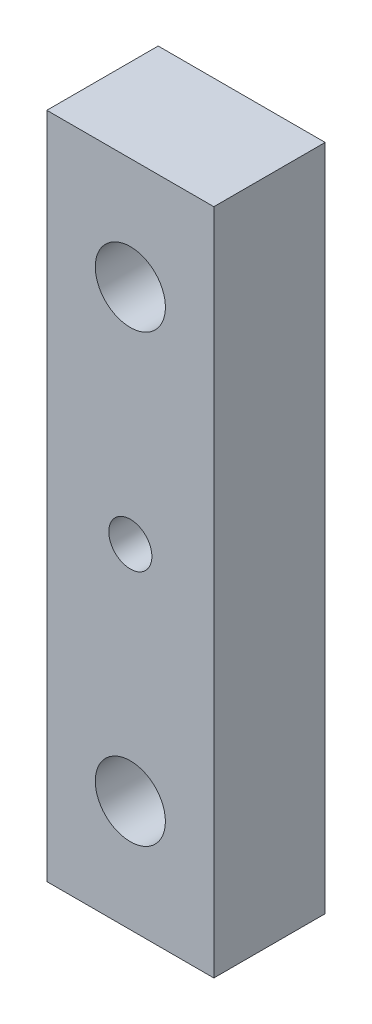
SolidWorks part; units mm, degrees
ref_plane "Front Plane" through (0, 0, 0) normal (0, 0, 1) x (1, 0, 0)
ref_plane "Top Plane" through (0, 0, 0) normal (0, 1, 0) x (1, 0, 0)
ref_plane "Right Plane" through (0, 0, 0) normal (1, 0, 0) x (0, 0, -1)
sketch "Sketch1" plane through (0, 0, 0) normal (0, 0, 1) x (1, 0, 0)
  line L1 (0, 0) -> (19.05, 0)
  line L2 (0, 0) -> (0, 76.2)
  line L3 (0, 76.2) -> (19.05, 76.2)
  line L4 (19.05, 0) -> (19.05, 76.2)
  dimension "D1" = 19.05
  dimension "D2" = 76.2
extrude "Extrude1" add sketch "Sketch1" along normal blind 12.7
sketch "Sketch2" plane through (0, 0, 12.7) normal (0, 0, 1) x (1, 0, 0)
  line L0 (9.525, 0) -> (9.525, 76.2) construction
  line L1 (0, 0) -> (19.05, 0) construction
  line L2 (19.05, 76.2) -> (0, 76.2) construction
  line L3 (0, 38.1) -> (19.05, 38.1) construction
  line L4 (0, 76.2) -> (0, 0) construction
  line L5 (19.05, 0) -> (19.05, 76.2) construction
  circle A0 centre (9.525, 12.7) radius 4
  circle A1 centre (9.525, 63.5) radius 4
  dimension "D1" = 8
  dimension "D2" = 25.4
extrude "Extrude2" cut sketch "Sketch2" against normal up to next
hole_wizard "#10 (0.1935) Diameter Hole1" positions "3DSketch1" profile "Sketch3" hole size "#10" standard "Ansi Inch" end condition up to next
sketch3d "3DSketch1"
  line L0 (9.525, 76.2, 12.7) -> (9.525, 0, 12.7)
  line L1 (19.05, 76.2, 12.7) -> (0, 76.2, 12.7) construction
  line L2 (0, 0, 12.7) -> (19.05, 0, 12.7) construction
  point P0 (9.525, 38.1, 12.7)
sketch "Sketch3" plane through (9.525, 38.1, 12.7) normal (1, 0, 0) x (0, -1, 0)
  line L0 (0, 0) -> (0, 12.7)
  line L1 (0, 12.7) -> (2.4574, 12.7)
  line L2 (2.4574, 12.7) -> (2.4574, 0)
  line L5 (2.4574, 0) -> (0, 0)
  line L11 (0, -6.35) -> (0, 107.95) construction
  dimension "Thru Hole Dia." = 4.9149
  dimension "Thru Hole Depth" = 12.7
